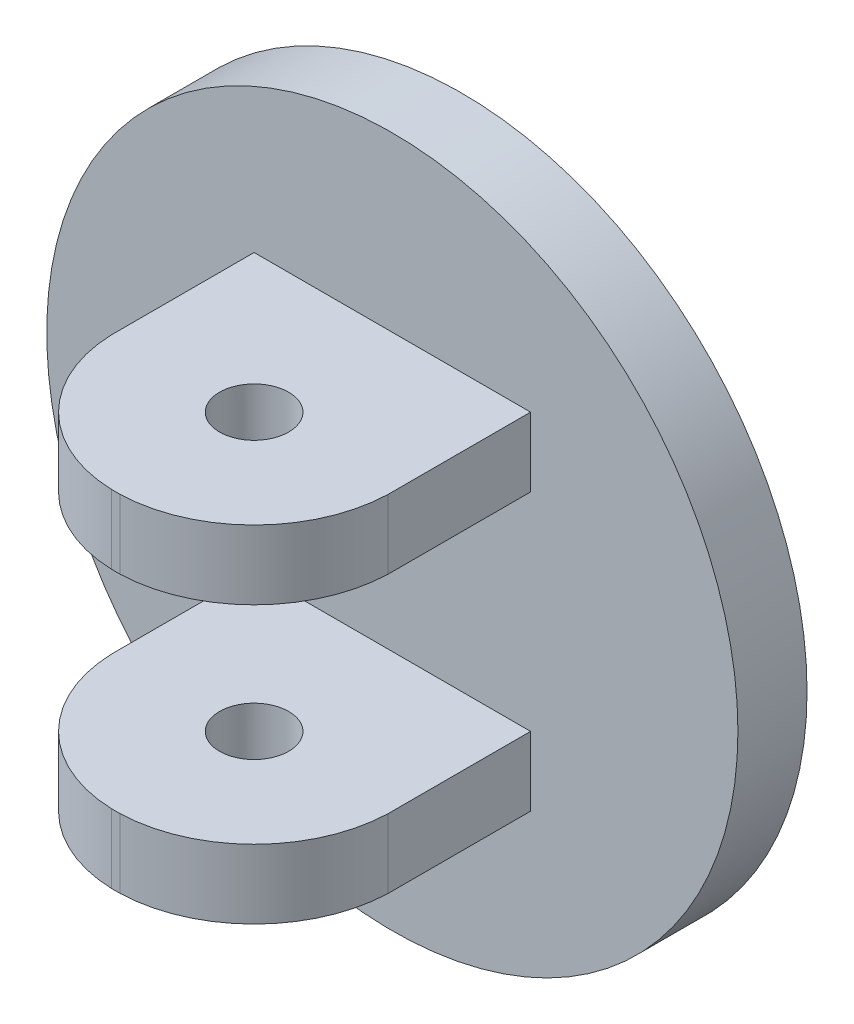
SolidWorks part; units mm, degrees
ref_plane "Front Plane" through (0, 0, 0) normal (0, 0, 1) x (1, 0, 0)
ref_plane "Top Plane" through (0, 0, 0) normal (0, 1, 0) x (1, 0, 0)
ref_plane "Right Plane" through (0, 0, 0) normal (1, 0, 0) x (0, 0, -1)
sketch "Sketch1" plane through (0, 0, 0) normal (0, 0, 1) x (1, 0, 0)
  circle A0 centre (0, 0) radius 50
  dimension "D1" = 100
extrude "Boss-Extrude1" add sketch "Sketch1" along normal blind 10
sketch "Sketch2" plane through (0, 0, 10) normal (0, 0, 1) x (1, 0, 0)
  line L2 (0, 15) -> (20, 15)
  line L4 (0, 25) -> (20, 25)
  line L5 (20, 15) -> (20, 25)
  line L6 (0, 15) -> (-20, 15)
  line L8 (0, 25) -> (-20, 25)
  line L9 (-20, 15) -> (-20, 25)
  line L10 (0, -15) -> (20, -15)
  line L12 (0, -25) -> (20, -25)
  line L13 (20, -15) -> (20, -25)
  line L14 (0, -15) -> (-20, -15)
  line L16 (0, -25) -> (-20, -25)
  line L17 (-20, -15) -> (-20, -25)
  point P4 (0, 0)
  dimension "D1" = 30
  dimension "D2" = 20
  dimension "D3" = 20
  dimension "D4" = 10
  dimension "D5" = 20
  dimension "D6" = 20
  dimension "D7" = 10
extrude "Boss-Extrude2" add sketch "Sketch2" along normal blind 40
sketch "Sketch3" plane through (0, 25, 0) normal (0, 1, 0) x (1, 0, 0)
  circle A0 centre (0, -30) radius 5
  dimension "D1" = 10
extrude "Cut-Extrude1" cut sketch "Sketch3" against normal blind 51 and the other way blind 10
sketch "Sketch4" plane through (0, -25, 0) normal (0, -1, 0) x (1, 0, 0)
  line L0 (20, 50) -> (20, 10) construction
  line L1 (-20, 30.6224) -> (-26.0021, 30.6224)
  line L2 (-26.0021, 30.6224) -> (-24.5261, 56.7262)
  line L3 (-24.5261, 56.7262) -> (26.1773, 55.3371)
  line L4 (26.1773, 55.3371) -> (30.1711, 28.5962)
  line L5 (30.1711, 28.5962) -> (20, 29.3776)
  arc A0 (20, 29.3776) -> (-20, 30.6224) centre (0, 30) ccw
extrude "Cut-Extrude2" cut sketch "Sketch4" against normal blind 51 and the other way blind 51
